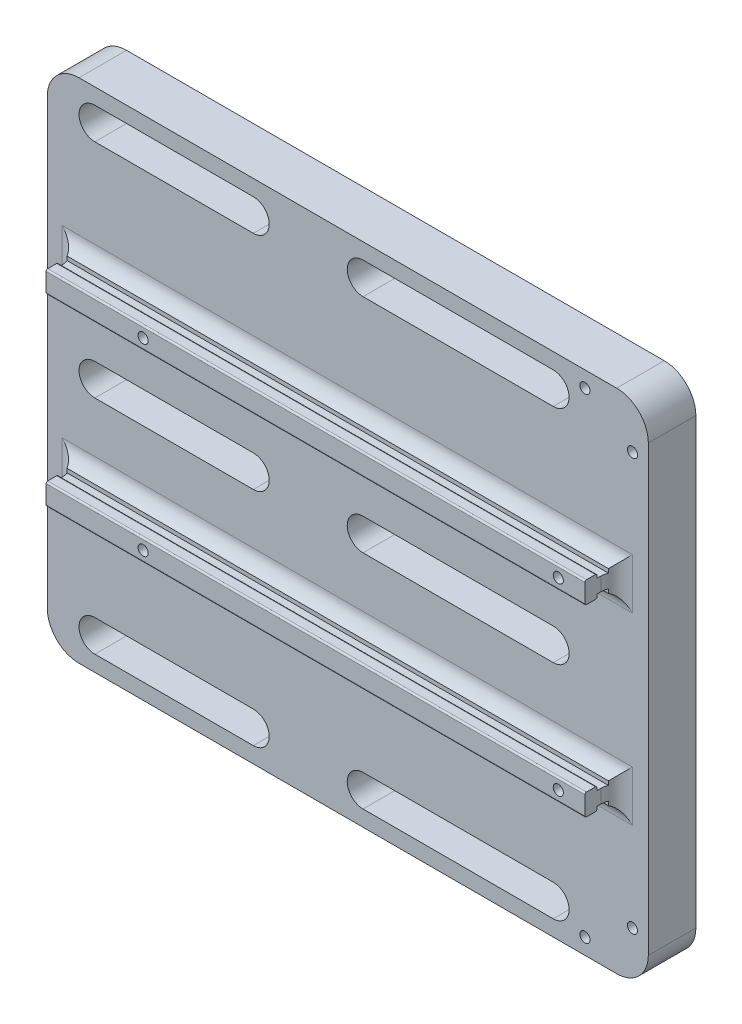
SolidWorks part; units mm, degrees
ref_plane "前视基准面" through (0, 0, 0) normal (0, 0, 1) x (1, 0, 0)
ref_plane "上视基准面" through (0, 0, 0) normal (0, 1, 0) x (1, 0, 0)
ref_plane "右视基准面" through (0, 0, 0) normal (1, 0, 0) x (0, 0, -1)
other "Configuration Table"
sketch "草图1" plane through (0, 0, 0) normal (0, 0, 1) x (1, 0, 0)
  line L0 (0, 0) -> (0, 26371.7997) construction
  line L1 (0, 0) -> (26371.7997, 0) construction
  line L3 (-125, 80) -> (125, 80)
  line L4 (-125, 80) -> (-125, -80)
  line L5 (-125, -80) -> (125, -80)
  line L6 (125, 80) -> (125, -80)
  line L7 (-125, 80) -> (125, -80) construction
  line L8 (-125, -80) -> (125, 80) construction
  point P5 (0, 0)
  dimension "D1" = 250
  dimension "D2" = 160
extrude "凸台-拉伸1" add sketch "草图1" along normal blind 15
sketch "草图2" plane through (0, 0, 15) normal (0, 0, 1) x (1, 0, 0)
  line L0 (0, 0) -> (50000, 0) construction
  line L1 (0, 0) -> (0, 50000) construction
  line L2 (125, -80) -> (125, 80) construction
  line L3 (-55, 32.4) -> (115, 32.4)
  line L4 (-55, 32.4) -> (-55, 25.6)
  line L5 (-55, 25.6) -> (115, 25.6)
  line L6 (115, 32.4) -> (115, 25.6)
  line L7 (-55, 32.4) -> (115, 25.6) construction
  line L8 (-55, 25.6) -> (115, 32.4) construction
  line L9 (-55, -25.6) -> (115, -25.6)
  line L10 (115, -32.4) -> (115, -25.6)
  line L11 (-55, -32.4) -> (-55, -25.6)
  line L12 (-55, -32.4) -> (115, -32.4)
  point P5 (30, 29)
  dimension "D1" = 29
  dimension "D2" = 170
  dimension "D3" = 10
  dimension "D4" = 6.8
extrude "凸台-拉伸2" add sketch "草图2" along normal blind 10
sketch "草图3" plane through (115, 0, 0) normal (1, 0, 0) x (0, 0, -1)
  line L0 (-25, 29) -> (-15, 29) construction
  line L1 (-25, 25.6) -> (-25, 32.4) construction
  line L2 (-15, 25.6) -> (-15, 32.4) construction
  line L3 (-25, 32.4) -> (-15, 32.4) construction
  line L4 (-21.2, 32.4) -> (-18, 32.4)
  line L5 (-21.2, 32.4) -> (-21.2, 31.15)
  line L6 (-21.2, 31.15) -> (-18, 31.15)
  line L7 (-18, 32.4) -> (-18, 31.15)
  line L8 (-21.2, 26.85) -> (-18, 26.85)
  line L9 (-18, 25.6) -> (-18, 26.85)
  line L10 (-21.2, 25.6) -> (-21.2, 26.85)
  line L11 (-21.2, 25.6) -> (-18, 25.6)
  dimension "D1" = 3.8
  dimension "D2" = 3.2
  dimension "D3" = 4.3
extrude "切除-拉伸1" cut sketch "草图3" against normal through all
fillet "圆角1" radius 0.5 4 edges at (30, 25.6, 21.2) (30, 25.6, 25) (30, 32.4, 25) (30, 32.4, 21.2)
sketch "草图4" plane through (115, 0, 0) normal (1, 0, 0) x (0, 0, -1)
  line L0 (-25, -29) -> (-15, -29) construction
  line L1 (-25, -32.4) -> (-25, -25.6) construction
  line L2 (-15, -32.4) -> (-15, -25.6) construction
  line L3 (-25, -25.6) -> (-15, -25.6) construction
  line L4 (-21.2, -25.6) -> (-18, -25.6)
  line L5 (-21.2, -25.6) -> (-21.2, -26.85)
  line L6 (-21.2, -26.85) -> (-18, -26.85)
  line L7 (-18, -25.6) -> (-18, -26.85)
  line L8 (-18, -32.4) -> (-18, -31.15)
  line L9 (-21.2, -31.15) -> (-18, -31.15)
  line L10 (-21.2, -32.4) -> (-21.2, -31.15)
  line L11 (-21.2, -32.4) -> (-18, -32.4)
  dimension "D1" = 3.8
  dimension "D2" = 3.2
  dimension "D3" = 4.3
extrude "切除-拉伸2" cut sketch "草图4" against normal through all
fillet "圆角2" radius 0.5 4 edges at (30, -32.4, 21.2) (30, -32.4, 25) (30, -25.6, 25) (30, -25.6, 21.2)
fillet "圆角3" radius 5 2 edges at (30, 25.6, 15) (30, 32.4, 15)
fillet "圆角4" radius 5 2 edges at (115, 29, 15) (-55, 29, 15)
fillet "圆角5" radius 5 4 edges at (-55, -29, 15) (115, -29, 15) (30, -25.6, 15) (30, -32.4, 15)
sketch "草图5" plane through (0, 0, 0) normal (0, 0, -1) x (-1, 0, 0)
  line L0 (-125, 0) -> (131.1555, 0) construction
  line L1 (-125, -80) -> (-125, 80) construction
  line L2 (-30, 29) -> (-115, 29) construction
  line L3 (-115, 32.4) -> (-115, 25.6) construction
  line L4 (-115, 29) -> (55, 29) construction
  line L5 (55, 32.4) -> (55, 25.6) construction
  circle A0 centre (-106.6, 29) radius 1.6
  circle A1 centre (24.4, 29) radius 1.6
  circle A2 centre (24.4, -29) radius 1.6
  circle A3 centre (-106.6, -29) radius 1.6
  dimension "D1" = 8.4
  dimension "D2" = 3.2
  dimension "D3" = 3.2
  dimension "D4" = 131
extrude "切除-拉伸3" cut sketch "草图5" against normal through all
sketch "草图6" plane through (0, 0, 0) normal (0, 0, -1) x (-1, 0, 0)
  line L0 (-125, 80) -> (-95, 80)
  line L1 (-125, 80) -> (125, 80) construction
  line L2 (-95, 80) -> (-95, 70)
  line L3 (-95, 70) -> (-115, 70)
  line L4 (-115, 70) -> (-115, 60)
  line L5 (-115, 60) -> (-125, 60)
  line L6 (-125, -80) -> (-125, 80) construction
  line L7 (-125, 60) -> (-125, 80)
  line L8 (0, 0) -> (50000, 0) construction
  line L9 (125, 80) -> (95, 80)
  line L10 (95, 80) -> (95, 70)
  line L11 (95, 70) -> (115, 70)
  line L12 (115, 70) -> (115, 60)
  line L13 (115, 60) -> (125, 60)
  line L14 (125, 80) -> (125, -80) construction
  line L15 (125, 60) -> (125, 80)
  line L16 (-125, -60) -> (-125, -80)
  line L17 (-115, -60) -> (-125, -60)
  line L18 (-115, -70) -> (-115, -60)
  line L19 (-95, -70) -> (-115, -70)
  line L20 (-95, -80) -> (-95, -70)
  line L21 (-125, -80) -> (-95, -80)
  line L22 (125, -60) -> (125, -80)
  line L23 (115, -60) -> (125, -60)
  line L24 (115, -70) -> (115, -60)
  line L25 (95, -70) -> (115, -70)
  line L26 (95, -80) -> (95, -70)
  line L27 (125, -80) -> (95, -80)
  circle A0 centre (-120, 65) radius 1.6
  circle A1 centre (-105, 75) radius 1.6
  circle A2 centre (105, 75) radius 1.6
  circle A3 centre (120, 65) radius 1.6
  circle A4 centre (120, -65) radius 1.6
  circle A5 centre (105, -75) radius 1.6
  circle A6 centre (-105, -75) radius 1.6
  circle A7 centre (-120, -65) radius 1.6
  dimension "D9" = 3.2
  dimension "D10" = 5
  dimension "D11" = 5
  dimension "D12" = 3.2
  dimension "D13" = 5
  dimension "D14" = 10
  dimension "D15" = 5
  dimension "D16" = 10
  dimension "D17" = 3.2
  dimension "D18" = 5
  dimension "D19" = 5
  dimension "D20" = 3.2
  dimension "D1" = 30
  dimension "D2" = 20
  dimension "D3" = 10
  dimension "D4" = 10
  dimension "D5" = 30
  dimension "D6" = 20
  dimension "D7" = 10
  dimension "D8" = 10
extrude "切除-拉伸4" cut sketch "草图6" against normal through all contours A5 | A4 | A3 | A2 | A1 | A0 | A7 | A6
sketch "草图9" plane through (0, 0, 0) normal (0, 0, -1) x (-1, 0, 0)
  circle A0 centre (-106.6, 29) radius 3
  circle A1 centre (24.4, 29) radius 3
  circle A2 centre (-106.6, -29) radius 3
  circle A3 centre (24.4, -29) radius 3
  dimension "D1" = 6
  dimension "D2" = 6
  dimension "D3" = 6
  dimension "D4" = 6
extrude "切除-拉伸6" cut sketch "草图9" against normal blind 3
sketch "草图10" plane through (0, 0, 15) normal (0, 0, 1) x (1, 0, 0)
  line L0 (-125, -80) -> (125, -80) construction
  line L1 (-125, 80) -> (-64.6266, 80)
  line L2 (-125, 80) -> (-125, -80)
  line L3 (-125, -80) -> (-64.6266, -80)
  line L4 (-64.6266, 80) -> (-64.6266, -80)
extrude "切除-拉伸7" cut sketch "草图10" against normal through all
sketch "草图11" plane through (0, 0, 0) normal (0, 0, -1) x (-1, 0, 0)
  line L0 (-200000, 0) -> (250000, 0) construction
  line L1 (-95, 5) -> (-35, 5)
  line L2 (-95, 5) -> (-95, -5) construction
  line L3 (-95, -5) -> (-35, -5)
  line L4 (-35, 5) -> (-35, -5) construction
  line L5 (-95, 5) -> (-35, -5) construction
  line L6 (-95, -5) -> (-35, 5) construction
  line L7 (-125, -80) -> (-125, 80) construction
  line L8 (64.6266, -80) -> (64.6266, 80) construction
  line L9 (-0.3734, 5) -> (49.6266, 5)
  line L10 (-0.3734, 5) -> (-0.3734, -5) construction
  line L11 (-0.3734, -5) -> (49.6266, -5)
  line L12 (49.6266, 5) -> (49.6266, -5) construction
  line L13 (-0.3734, 5) -> (49.6266, -5) construction
  line L14 (-0.3734, -5) -> (49.6266, 5) construction
  line L15 (-95, 75) -> (-35, 75)
  line L16 (-95, 65) -> (-35, 65)
  line L17 (-0.3734, 75) -> (49.6266, 75)
  line L18 (-0.3734, 65) -> (49.6266, 65)
  line L19 (-95, 75) -> (-95, 65) construction
  line L20 (-35, 75) -> (-35, 65) construction
  line L21 (-95, 75) -> (-35, 65) construction
  line L22 (-95, 65) -> (-35, 75) construction
  line L23 (-0.3734, 75) -> (-0.3734, 65) construction
  line L24 (49.6266, 75) -> (49.6266, 65) construction
  line L25 (-0.3734, 75) -> (49.6266, 65) construction
  line L26 (-0.3734, 65) -> (49.6266, 75) construction
  line L27 (-95, -65) -> (-35, -65)
  line L28 (-95, -75) -> (-35, -75)
  line L29 (-0.3734, -65) -> (49.6266, -65)
  line L30 (-0.3734, -75) -> (49.6266, -75)
  line L31 (-95, -65) -> (-95, -75) construction
  line L32 (-35, -65) -> (-35, -75) construction
  line L33 (-95, -65) -> (-35, -75) construction
  line L34 (-95, -75) -> (-35, -65) construction
  line L35 (-0.3734, -65) -> (-0.3734, -75) construction
  line L36 (49.6266, -65) -> (49.6266, -75) construction
  line L37 (-0.3734, -65) -> (49.6266, -75) construction
  line L38 (-0.3734, -75) -> (49.6266, -65) construction
  arc A0 (-95, 5) -> (-95, -5) centre (-95, 0) ccw
  arc A1 (-35, -5) -> (-35, 5) centre (-35, 0) ccw
  arc A2 (-0.3734, 5) -> (-0.3734, -5) centre (-0.3734, 0) ccw
  arc A3 (49.6266, -5) -> (49.6266, 5) centre (49.6266, 0) ccw
  arc A4 (-95, 75) -> (-95, 65) centre (-95, 70) ccw
  arc A5 (-35, 65) -> (-35, 75) centre (-35, 70) ccw
  arc A6 (-0.3734, 75) -> (-0.3734, 65) centre (-0.3734, 70) ccw
  arc A7 (49.6266, 65) -> (49.6266, 75) centre (49.6266, 70) ccw
  arc A8 (-95, -65) -> (-95, -75) centre (-95, -70) ccw
  arc A9 (-35, -75) -> (-35, -65) centre (-35, -70) ccw
  arc A10 (-0.3734, -65) -> (-0.3734, -75) centre (-0.3734, -70) ccw
  arc A11 (49.6266, -75) -> (49.6266, -65) centre (49.6266, -70) ccw
  point P0 (-65, 0)
  point P9 (24.6266, 0)
  point P21 (-65, -70)
  point P22 (-65, 70)
  point P27 (24.6266, 70)
  point P40 (24.6266, -70)
  dimension "D1" = 60
  dimension "D2" = 10
  dimension "D3" = 60
  dimension "D4" = 40
  dimension "D5" = 10
  dimension "D6" = 50
  dimension "D7" = 2
  dimension "D8" = 2
extrude "切除-拉伸8" cut sketch "草图11" against normal through all
fillet "圆角6" radius 10 4 edges at (-64.6266, -80, 7.5) (125, -80, 7.5) (125, 80, 7.5) (-64.6266, 80, 7.5)
sketch "草图12" plane through (0, 0, 0) normal (0, 0, -1) x (-1, 0, 0)
  line L0 (-125, 40) -> (64.6266, 40) construction
  line L1 (-125, -70) -> (-125, 70) construction
  line L2 (64.6266, -70) -> (64.6266, 70) construction
  line L3 (-200000, 0) -> (250000, 0) construction
  text T0 "GIFT @ SJTU\r\nZhe Chen" font "Times New Roman" height 3.5
  dimension "D1" = 40
extrude "切除-拉伸9" cut sketch "草图12" against normal blind 5
